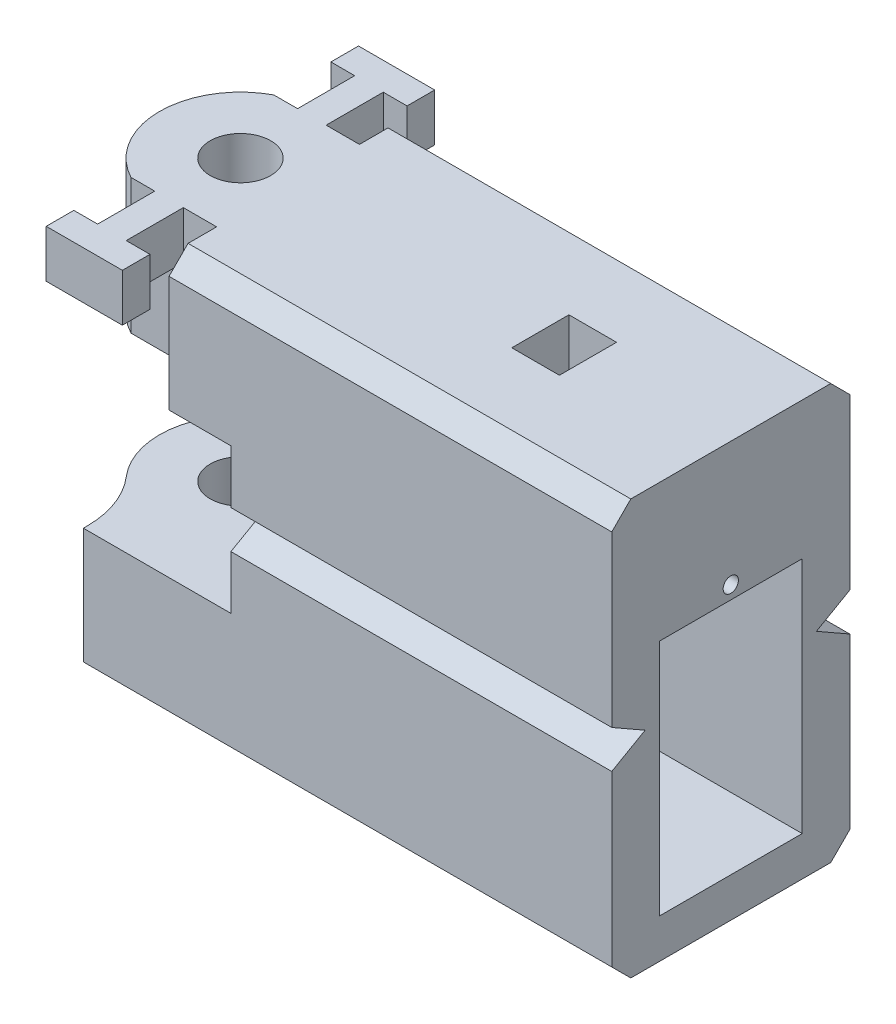
SolidWorks part; units mm, degrees
ref_plane "Front Plane" through (0, 0, 0) normal (0, 0, 1) x (1, 0, 0)
ref_plane "Top Plane" through (0, 0, 0) normal (0, 1, 0) x (1, 0, 0)
ref_plane "Right Plane" through (0, 0, 0) normal (1, 0, 0) x (0, 0, -1)
sketch "Sketch1" plane through (0, 0, 0) normal (1, 0, 0) x (0, 0, -1)
  line L0 (3.5, 21.787) -> (21.5, 21.787) construction
  line L1 (0, 0) -> (25, 0)
  line L2 (0, 0) -> (0, 19.787)
  line L3 (0, 43.574) -> (25, 43.574)
  line L4 (25, 0) -> (25, 19.787)
  line L5 (0, 23.787) -> (3.5, 21.787)
  line L6 (0, 19.787) -> (3.5, 21.787)
  line L7 (12.5, 43.574) -> (12.5, 0) construction
  line L8 (25, 23.787) -> (21.5, 21.787)
  line L9 (25, 19.787) -> (21.5, 21.787)
  line L10 (0, 23.787) -> (0, 43.574)
  line L11 (25, 23.787) -> (25, 43.574)
  point P6 (12.5, 21.787)
  dimension "D1" = 43.574
  dimension "D2" = 25
  dimension "D3" = 4
  dimension "D4" = 18
extrude "Boss-Extrude1" add sketch "Sketch1" along normal blind 55.5
chamfer "Chamfer1" distance 2 angle 45 4 edges at (27.75, 43.574, -25) (27.75, 43.574, 0) (27.75, 0, -25) (27.75, 0, 0)
sketch "Sketch4" plane through (0, 43.574, 0) normal (0, 1, 0) x (1, 0, 0)
  line L5 (0, 23) -> (0, 2) construction
  line L11 (0, 28.9) -> (8, 28.9)
  line L30 (0, 28.9) -> (0, -3.9)
  line L31 (0, -3.9) -> (8, -3.9)
  line L32 (8, 28.9) -> (8, -3.9)
  point P6 (0, 12.5)
  dimension "D1" = 32.8
  dimension "D2" = 8
extrude "Boss-Extrude2" add sketch "Sketch4" against normal blind 5
sketch "Sketch7" plane through (0, 43.574, 0) normal (0, 1, 0) x (1, 0, 0)
  line L0 (4, 28.9) -> (4, -3.9) construction
  line L1 (8, 28.9) -> (0, 28.9) construction
  line L2 (0, -3.9) -> (8, -3.9) construction
  line L3 (55.5, 12.5) -> (0, 12.5) construction
  line L4 (55.5, 23) -> (55.5, 2) construction
  line L5 (0, 28.9) -> (0, -3.9) construction
  line L6 (9, 5) -> (5.5, 5)
  line L7 (9, 26) -> (5.5, 26)
  line L8 (9, 26) -> (9, 20)
  line L9 (9, 20) -> (5.5, 20)
  line L10 (5.5, 26) -> (5.5, 20)
  line L11 (5.5, 23) -> (5.5, 12.5) construction
  line L12 (5.5, -1) -> (5.5, 5)
  line L13 (9, -1) -> (5.5, -1)
  line L14 (9, -1) -> (9, 5)
  line L15 (-1, -1) -> (-1, 5)
  line L16 (-1, -1) -> (2.5, -1)
  line L17 (2.5, -1) -> (2.5, 5)
  line L18 (-1, 5) -> (2.5, 5)
  line L19 (-1, 20) -> (2.5, 20)
  line L20 (2.5, 26) -> (2.5, 20)
  line L21 (-1, 26) -> (2.5, 26)
  line L22 (-1, 26) -> (-1, 20)
  dimension "D1" = 6
  dimension "D2" = 1.5
  dimension "D3" = 10.5
  dimension "D4" = 3.5
extrude "Cut-Extrude5" cut sketch "Sketch7" against normal blind 10
sketch "Sketch5" plane through (0, 43.574, 0) normal (0, 1, 0) x (1, 0, 0)
  line L0 (4, 28.9) -> (4, -3.9) construction
  line L1 (8, 28.9) -> (0, 28.9) construction
  line L2 (0, -3.9) -> (8, -3.9) construction
  circle A0 centre (4, 12.5) radius 1 construction
  circle A1 centre (4, 12.5) radius 3.175
  dimension "D1" = 2
  dimension "D2" = 6.35
extrude "Cut-Extrude3" cut sketch "Sketch5" against normal through all contours A1
ref_plane "Plane1" through (0, 21.787, 0) normal (0, -1, 0) x (-1, 0, 0)
sketch "Sketch6" plane through (0, 21.787, 0) normal (0, -1, 0) x (-1, 0, 0)
  line L6 (-4, 30) -> (4.5, 30)
  line L7 (4.5, 30) -> (4.5, -5)
  line L9 (4.5, -5) -> (-4, -5)
  line L10 (-15.5, -5) -> (-15.5, 30)
  line L11 (-15.5, 30) -> (-4, 30)
  line L12 (-15.5, -5) -> (-4, -5)
  circle A1 centre (-4, 12.5) radius 3.175 construction
  circle A5 centre (-4, 12.5) radius 3.175
  dimension "D1" = 15.5
  dimension "D2" = 20
  dimension "D3" = 35
  dimension "D4" = 17.5
extrude "Cut-Extrude4" cut sketch "Sketch6" against normal mid plane 15.24
sketch "Sketch8" plane through (0, 29.407, 0) normal (0, -1, 0) x (1, 0, 0)
  line L0 (9, 0) -> (9, -5) construction
  line L9 (9, -20) -> (9, -25) construction
  line L10 (9, 0) -> (9, -5)
  line L11 (9, -20) -> (9, -25)
  line L13 (9, -20) -> (0, -20)
  line L14 (9, -20) -> (9, -25)
  line L15 (9, -25) -> (0, -25)
  line L16 (0, -20) -> (0, -25)
  line L17 (9, -5) -> (0, -5)
  line L18 (9, -5) -> (9, 0)
  line L19 (9, 0) -> (0, 0)
  line L20 (0, -5) -> (0, 0)
  line M8 (15.5, 0) -> (0, 0)
  line M11 (0, 0) -> (0, -25)
  line M14 (0, -25) -> (15.5, -25)
extrude "Cut-Extrude6" cut sketch "Sketch8" against normal up to surface (9.167 mm away) contours L11 L13 M11 M14 | L17 L10 M8 M11 region at (4.5, 29.407, -22.5) region at (4.5, 29.407, -2.5) up to face at (4, 38.574, 1.475)
sketch "Sketch9" plane through (0, 43.574, 0) normal (0, 1, 0) x (1, 0, 0)
  line L0 (0, 20) -> (0, 5)
  arc A0 (0, 20) -> (0, 5) centre (4, 12.5) ccw
extrude "Boss-Extrude3" add sketch "Sketch9" against normal up to surface (14.167 mm away) up to face at (8.375, 29.407, -12.5)
extrude "Boss-Extrude4" add sketch "Sketch9<2>" along direction (0, 1, 0) on the side against the normal up to surface (43.574 mm away) from surface up to face at (4, 0, -9.325) starting at face at (4, 14.167, -15.675)
sketch "Sketch9<2>" plane through (0, 43.574, 0) normal (0, 1, 0) x (1, 0, 0) same geometry as "Sketch9"
fillet "Fillet1" radius 10 2 edges at (0, 7.0835, -20) (0, 7.0835, -5)
sketch "Sketch10" plane through (55.5, 0, 0) normal (1, 0, 0) x (0, 0, -1)
  line L0 (21.5, 21.787) -> (3.5, 21.787) construction
  line L1 (5, 29.137) -> (20, 29.137)
  line L2 (5, 29.137) -> (5, 4.137)
  line L3 (5, 4.137) -> (20, 4.137)
  line L4 (20, 29.137) -> (20, 4.137)
  line L5 (12.5, 43.574) -> (12.5, 4.137) construction
  line L6 (23, 43.574) -> (2, 43.574) construction
  line L8 (12.5, 29.137) -> (12.5, 21.787) construction
  line L9 (5, 16.637) -> (20, 16.637) construction
  circle A0 centre (12.5, 21.787) radius 2.5 construction
  point P9 (36.3907, 4.137)
  point P12 (19.6616, 4.137)
  point P15 (14.5, 4.137)
  point P22 (12.5, 25.462)
  dimension "D3" = 5
  dimension "D1" = 25
  dimension "D2" = 15
  dimension "D4" = 5.15
extrude "Cut-Extrude7" cut sketch "Sketch10" against normal blind 20
sketch "Sketch11" plane through (55.5, 0, 0) normal (1, 0, 0) x (0, 0, -1)
  line L0 (12.5, 43.574) -> (12.5, 30.537) construction
  line L1 (23, 43.574) -> (2, 43.574) construction
  circle A0 centre (12.5, 30.537) radius 0.8
  dimension "D2" = 1.6
  dimension "D1" = 8.75
extrude "Cut-Extrude8" cut sketch "Sketch11" against normal blind 8
sketch "Sketch12" plane through (0, 43.574, 0) normal (0, 1, 0) x (1, 0, 0)
  line L0 (40.5, 12.5) -> (55.5, 12.5) construction
  line L1 (40.5, 15.5) -> (35.5, 15.5)
  line L2 (40.5, 15.5) -> (40.5, 9.5)
  line L3 (40.5, 9.5) -> (35.5, 9.5)
  line L4 (55.5, 5) -> (55.5, 20)
  line L5 (35.5, 5) -> (55.5, 5)
  line L6 (35.5, 20) -> (35.5, 5)
  line L7 (55.5, 20) -> (35.5, 20)
  line L8 (55.5, 5) -> (55.5, 20)
  line L9 (35.5, 5) -> (55.5, 5)
  line L10 (35.5, 20) -> (35.5, 5)
  line L11 (55.5, 20) -> (35.5, 20)
  line L12 (35.5, 15.5) -> (35.5, 9.5)
  dimension "D2" = 15
  dimension "D3" = 6
  dimension "D1" = 0
extrude "Cut-Extrude9" cut sketch "Sketch12" against normal up to surface (14.437 mm away) contours L1 L10 L3 L2 region at (38, 43.574, -12.5) up to face at (45.5, 29.137, -12.5)
